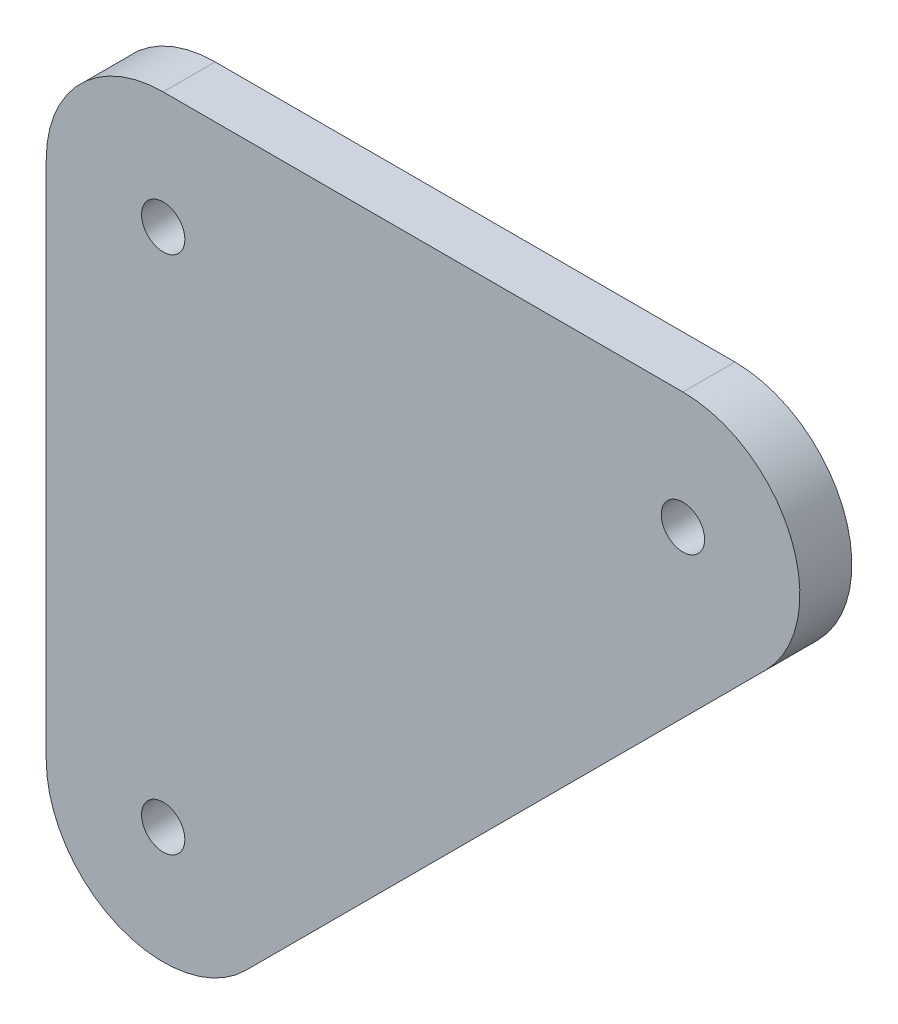
SolidWorks part; units mm, degrees
ref_plane "Plano frontal" through (0, 0, 0) normal (0, 0, 1) x (1, 0, 0)
ref_plane "Plano superior" through (0, 0, 0) normal (0, 1, 0) x (1, 0, 0)
ref_plane "Plano direito" through (0, 0, 0) normal (1, 0, 0) x (0, 0, -1)
sketch "Esboço1" plane through (0, 0, 0) normal (0, 0, 1) x (1, 0, 0)
  line L1 (-30, 30) -> (30, 30) construction
  line L2 (-30, 30) -> (-30, -30) construction
  line L3 (-30, -30) -> (30, -30) construction
  line L4 (30, 30) -> (30, -30) construction
  line L5 (-30, 30) -> (30, -30) construction
  line L6 (-30, -30) -> (30, 30) construction
  line L8 (30, 43.5) -> (-30, 43.5)
  line L23 (-20.4541, -39.5459) -> (39.5459, 20.4541)
  line L26 (-43.5, -30) -> (-43.5, 30)
  circle A0 centre (-30, 30) radius 2.5
  circle A1 centre (-30, -30) radius 2.5
  circle A2 centre (30, 30) radius 2.5
  arc A3 (-30, 43.5) -> (-43.5, 30) centre (-30, 30) ccw
  arc A5 (39.5459, 20.4541) -> (30, 43.5) centre (30, 30) ccw
  circle A7 centre (30, 30) radius 13.5 construction
  arc A8 (-43.5, -30) -> (-20.4541, -39.5459) centre (-30, -30) ccw
  circle A9 centre (-30, 30) radius 13.5 construction
  point P0 (0, 0)
  point P12 (-30, -30)
  point P13 (-20, 22.5)
  point P15 (-20, -22.5)
  point P20 (44, 0)
  point P34 (-81.0386, -15.474)
  point P36 (-81.0386, 15.2242)
  point P37 (-74.2886, -15.474)
  point P43 (-74.2886, 15.2242)
  dimension "D3" = 5
  dimension "D1" = 60
  dimension "D2" = 60
  dimension "D5" = 60
  dimension "D4" = 11
extrude "Ressalto-extrusão1" add sketch "Esboço1" along normal blind 6
ref_axis "Eixo1" through (-30, 30, 6) along (0, 0, -1)
ref_axis "Eixo2" through (30, 30, 6) along (0, 0, -1)
ref_plane "Plano1" through (0, 30, 0) normal (0, 1, 0) x (1, 0, 0)
